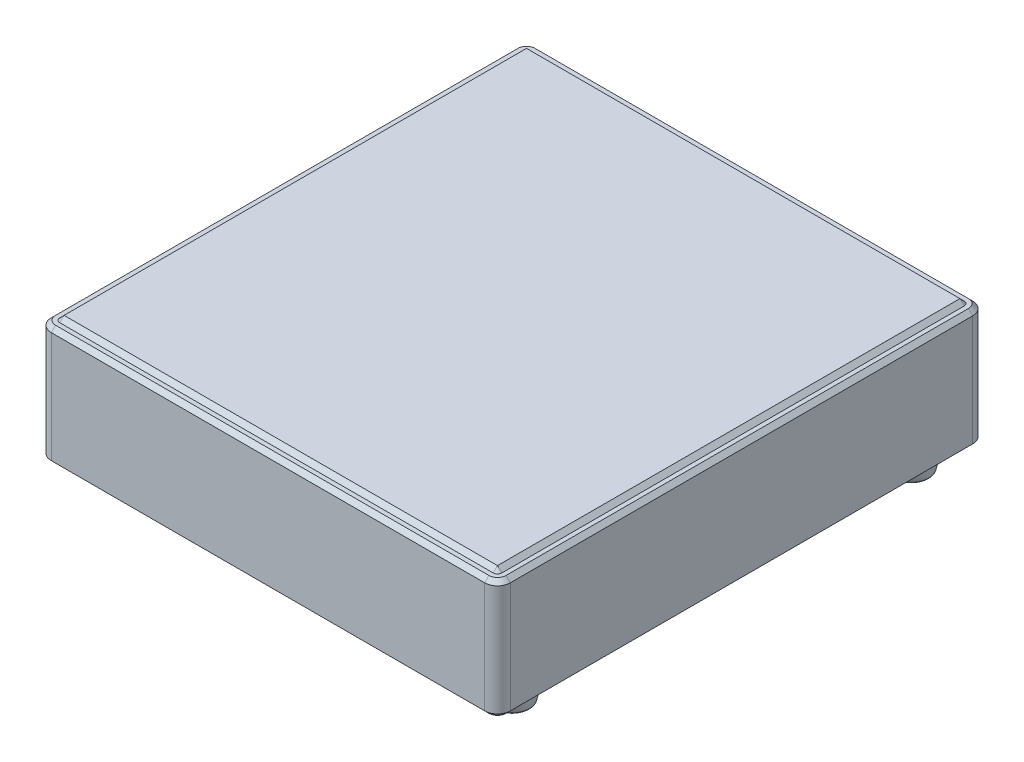
SolidWorks part; units mm, degrees
material "1060 Alloy"
ref_plane "Front Plane" through (0, 0, 0) normal (0, 0, 1) x (1, 0, 0)
ref_plane "Top Plane" through (0, 0, 0) normal (0, 1, 0) x (1, 0, 0)
ref_plane "Right Plane" through (0, 0, 0) normal (1, 0, 0) x (0, 0, -1)
sketch "Sketch1" plane through (0, 0, 0) normal (0, 1, 0) x (1, 0, 0)
  line L1 (0, 0) -> (107.6, 0)
  line L2 (0, 0) -> (0, 114.4)
  line L3 (0, 114.4) -> (107.6, 114.4)
  line L4 (107.6, 0) -> (107.6, 114.4)
  dimension "D1" = 114.4
  dimension "D2" = 107.6
extrude "Boss-Extrude1" add sketch "Sketch1" along normal blind 30
sketch "Sketch2" plane through (0, 0, 0) normal (0, -1, 0) x (1, 0, 0)
  line L0 (0, -114.4) -> (0, 0) construction
  line L1 (107.6, -114.4) -> (0, -114.4) construction
  circle A0 centre (7, -104) radius 1.5
  circle A1 centre (100.6, -104) radius 1.5
  circle A2 centre (100.6, -10.4) radius 1.5
  circle A3 centre (7, -10.4) radius 1.5
  circle A4 centre (53.8, -17.2) radius 1.5
  circle A5 centre (53.8, -97.2) radius 1.5
  dimension "D1" = 3
  dimension "D2" = 93.6
  dimension "D3" = 93.6
  dimension "D4" = 7
  dimension "D5" = 10.4
  dimension "D6" = 53.8
  dimension "D7" = 80
  dimension "D8" = 17.2
extrude "Cut-Extrude1" cut sketch "Sketch2" against normal blind 10
sketch "Sketch3" plane through (0, 0, 0) normal (0, -1, 0) x (1, 0, 0)
  circle A0 centre (7, -104) radius 4.5
  circle A1 centre (7, -104) radius 2.75
  dimension "D1" = 9
  dimension "D2" = 5.5
extrude "Boss-Extrude2" add sketch "Sketch3" along normal blind 3
ref_axis "Axis1" through (7, -3, -104) along (0, 1, 0)
ref_plane "Plane1" through (7, 0, 0) normal (1, 0, 0) x (0, 0, -1)
sketch "Sketch8" plane through (7, 0, 0) normal (1, 0, 0) x (0, 0, -1)
  line L0 (108.5, 0) -> (108.5, -3)
  line L1 (108.5, -3) -> (108, -3)
  line L2 (99.5, -3) -> (108.5, -3) construction
  arc A0 (108, -3) -> (108.5, 0) centre (99.25, 0) ccw
  dimension "D1" = 0.5
revolve "Cut-Revolve1" cut sketch "Sketch8" angle 360 about axis through (7, -3, -104) along (0, 1, 0)
fillet "Fillet5" radius 0.5 1 edges at (7, -3, -108)
sketch "Sketch9" plane through (0, 0, 0) normal (0, -1, 0) x (-1, 0, 0)
  point P0 (-7, 10.4)
  point P1 (-100.6, 10.4)
  point P3 (-100.6, 104)
pattern_sketch "Sketch-Pattern1" of "Boss-Extrude2", "Cut-Revolve1", "Fillet5" driven by "Sketch9"
fillet "Fillet2" radius 3 4 edges at (0, 15, -114.4) (107.6, 15, -114.4) (107.6, 15, 0) (0, 15, 0)
sketch "Sketch6" plane through (0, 30, 0) normal (0, 1, 0) x (1, 0, 0)
  line L24 (2, 111.4) -> (2, 3)
  line L25 (104.6, 112.4) -> (3, 112.4)
  line L26 (105.6, 3) -> (105.6, 111.4)
  line L27 (3, 2) -> (104.6, 2)
  line L28 (2, 111.4) -> (2, 3)
  line L29 (104.6, 112.4) -> (3, 112.4)
  line L30 (105.6, 3) -> (105.6, 111.4)
  line L31 (3, 2) -> (104.6, 2)
  arc A20 (2, 3) -> (3, 2) centre (3, 3) ccw
  arc A21 (3, 112.4) -> (2, 111.4) centre (3, 111.4) ccw
  arc A22 (105.6, 111.4) -> (104.6, 112.4) centre (104.6, 111.4) ccw
  arc A23 (104.6, 2) -> (105.6, 3) centre (104.6, 3) ccw
  arc A24 (2, 3) -> (3, 2) centre (3, 3) ccw
  arc A25 (3, 112.4) -> (2, 111.4) centre (3, 111.4) ccw
  arc A26 (105.6, 111.4) -> (104.6, 112.4) centre (104.6, 111.4) ccw
  arc A27 (104.6, 2) -> (105.6, 3) centre (104.6, 3) ccw
  dimension "D1" = 2
extrude "Cut-Extrude2" cut sketch "Sketch6" against normal blind 1 flip side to cut
sketch "Sketch7" plane through (0, 0, 0) normal (0, -1, 0) x (1, 0, 0)
  line L24 (105.6, -111.4) -> (105.6, -3)
  line L25 (3, -112.4) -> (104.6, -112.4)
  line L26 (2, -3) -> (2, -111.4)
  line L27 (104.6, -2) -> (3, -2)
  line L28 (105.6, -111.4) -> (105.6, -3)
  line L29 (3, -112.4) -> (104.6, -112.4)
  line L30 (2, -3) -> (2, -111.4)
  line L31 (104.6, -2) -> (3, -2)
  arc A20 (105.6, -3) -> (104.6, -2) centre (104.6, -3) ccw
  arc A21 (104.6, -112.4) -> (105.6, -111.4) centre (104.6, -111.4) ccw
  arc A22 (2, -111.4) -> (3, -112.4) centre (3, -111.4) ccw
  arc A23 (3, -2) -> (2, -3) centre (3, -3) ccw
  arc A24 (105.6, -3) -> (104.6, -2) centre (104.6, -3) ccw
  arc A25 (104.6, -112.4) -> (105.6, -111.4) centre (104.6, -111.4) ccw
  arc A26 (2, -111.4) -> (3, -112.4) centre (3, -111.4) ccw
  arc A27 (3, -2) -> (2, -3) centre (3, -3) ccw
  dimension "D1" = 2
extrude "Cut-Extrude3" cut sketch "Sketch7" against normal blind 1 flip side to cut
chamfer "Chamfer1" distance 1 angle 45 16 edges at (53.8, 1, -114.4) (106.7213, 1, -113.5213) (0.8787, 1, -113.5213) (107.6, 1, -57.2) (0, 1, -57.2) (106.7213, 1, -0.8787) (0.8787, 1, -0.8787) (53.8, 1, 0) (53.8, 29, -114.4) (0.8787, 29, -113.5213) (106.7213, 29, -113.5213) (0, 29, -57.2) (107.6, 29, -57.2) (0.8787, 29, -0.8787) (106.7213, 29, -0.8787) (53.8, 29, 0)
chamfer "Chamfer2" distance 1 angle 45 8 edges at (53.8, 30, -112.4) (2.2929, 30, -112.1071) (105.3071, 30, -112.1071) (2, 30, -57.2) (105.6, 30, -57.2) (2.2929, 30, -2.2929) (105.3071, 30, -2.2929) (53.8, 30, -2)
fillet "Fillet4" radius 0.5 8 edges at (105.3071, 0, -2.2929) (105.6, 0, -57.2) (105.3071, 0, -112.1071) (53.8, 0, -112.4) (2.2929, 0, -112.1071) (2, 0, -57.2) (2.2929, 0, -2.2929) (53.8, 0, -2)
